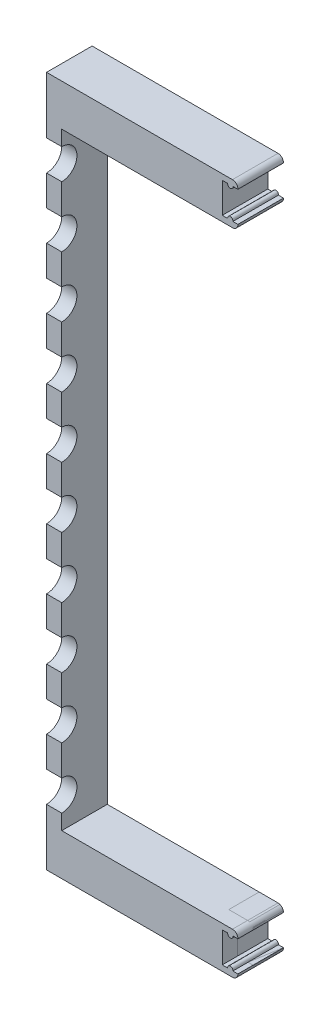
SolidWorks part; units mm, degrees
ref_plane "Front Plane" through (0, 0, 0) normal (0, 0, 1) x (1, 0, 0)
ref_plane "Top Plane" through (0, 0, 0) normal (0, 1, 0) x (1, 0, 0)
ref_plane "Right Plane" through (0, 0, 0) normal (1, 0, 0) x (0, 0, -1)
sketch "Sketch4" plane through (0, 0, 0) normal (0, 0, 1) x (1, 0, 0)
  line L0 (0, 0) -> (0, 13.7)
  line L1 (0, 13.7) -> (6.2, 13.7)
  line L2 (8, 11.9) -> (8, 11.85)
  line L4 (8, 11.85) -> (2.85, 11.85)
  line L5 (2.85, 11.85) -> (2.85, 1.85)
  line L6 (2.85, 1.85) -> (8, 1.85)
  line L10 (5.5, 11.85) -> (5.5, 13.7) construction
  line L14 (8, 1.85) -> (8, 1.8)
  line L15 (6.2, 0) -> (0, 0)
  line L16 (2.85, 6.85) -> (8, 6.85) construction
  line L17 (0, 0) -> (-55, 0)
  line L18 (-55, 0) -> (-55, 227.4)
  line L19 (-55, 113.7) -> (0, 113.7) construction
  line L20 (-55, 113.7) -> (-50, 113.7)
  line L21 (0, 113.7) -> (0, 0) construction
  line L22 (-50, 213.7) -> (-50, 13.7)
  line L23 (-50, 13.7) -> (0, 13.7)
  line L24 (2.85, 220.55) -> (8, 220.55) construction
  line L25 (5.5, 215.55) -> (5.5, 213.7) construction
  line L26 (-50, 213.7) -> (0, 213.7)
  line L27 (0, 227.4) -> (-55, 227.4)
  line L28 (6.2, 227.4) -> (0, 227.4)
  line L29 (8, 225.55) -> (8, 225.6)
  line L30 (-50, 227.4) -> (-50, 0) construction
  line L31 (2.85, 225.55) -> (8, 225.55)
  line L32 (2.85, 215.55) -> (2.85, 225.55)
  line L33 (8, 215.55) -> (2.85, 215.55)
  line L35 (8, 215.5) -> (8, 215.55)
  line L36 (0, 213.7) -> (6.2, 213.7)
  line L37 (0, 227.4) -> (0, 213.7)
  arc A2 (4.6633, 11.85) -> (6.3367, 11.85) centre (5.5, 11.7) ccw
  arc A3 (4.6633, 1.85) -> (6.3367, 1.85) centre (5.5, 2) cw
  arc A4 (8, 11.9) -> (6.2, 13.7) centre (6.2, 11.9) ccw
  arc A5 (6.2, 0) -> (8, 1.8) centre (6.2, 1.8) ccw
  arc A12 (6.2, 227.4) -> (8, 225.6) centre (6.2, 225.6) cw
  arc A13 (8, 215.5) -> (6.2, 213.7) centre (6.2, 215.5) cw
  arc A14 (4.6633, 225.55) -> (6.3367, 225.55) centre (5.5, 225.4) ccw
  arc A15 (4.6633, 215.55) -> (6.3367, 215.55) centre (5.5, 215.7) cw
  point P7 (2.85, 6.85)
  point P15 (8, 13.7)
  point P26 (8, 13.7)
  point P29 (8, 0)
  point P37 (0, 13.7)
  point P40 (0, 0)
  point P73 (8, 227.4)
  point P74 (8, 213.7)
  dimension "D6" = 50
  dimension "D8" = 0.15
  dimension "D9" = 0.85
  dimension "D11" = 1.8
  dimension "D12" = 1.8
  dimension "D15" = 100
  dimension "D1" = 13.7
  dimension "D2" = 8
  dimension "D3" = 1.85
  dimension "D4" = 2.85
  dimension "D5" = 10
  dimension "D7" = 1.85
  dimension "D10" = 2.65
  dimension "D17" = 5
extrude "Boss-Extrude1" add sketch "Sketch4" along normal blind 10 contours L15 A5 L14 L6 L5 L4 L2 A4 L1 L0 | L4 A2 | A3 L6 region at (2.6177, 6.85, 0) region at (5.5, 2.2812, 0) region at (5.5, 11.4188, 0)
extrude "Boss-Extrude2" add sketch "Sketch4<5>" along normal blind 15 separate body contours L15 A5 L14 L6 L5 L4 L2 A4 L1 L0 | L23 L22 L20 L18 L17 L0 | L37 L27 L18 L20 L22 L26 | A13 L35 L33 L32 L31 L29 A12 L28 L37 L36 | L31 A14 | A15 L33 | A3 L6 | L4 A2 region at (-27.5, 1.263, 0) region at (2.6177, 6.85, 0) region at (-53.737, 170.55, 0) region at (5.5, 2.2812, 0) region at (2.6177, 220.55, 0) region at (5.5, 11.4188, 0) region at (5.5, 225.1188, 0) region at (5.5, 215.9812, 0)
sketch "Sketch4<5>" plane through (0, 0, 0) normal (0, 0, 1) x (1, 0, 0) same geometry as "Sketch4"
sketch "Sketch5" plane through (-55, 0, 0) normal (-1, 0, 0) x (0, 0, 1)
  line L0 (15, 113.7) -> (0, 113.7) construction
  line L1 (15, 0) -> (15, 227.4) construction
  line L2 (0, 0) -> (0, 227.4) construction
  line L3 (15, 113.7) -> (15, 108.7) construction
  line L4 (15, 88.7) -> (15, 78.7)
  line L5 (15, 108.7) -> (15, 98.7)
  line L6 (15, 68.7) -> (15, 58.7)
  line L7 (15, 48.7) -> (15, 38.7)
  line L8 (15, 28.7) -> (15, 18.7)
  line L9 (15, 98.7) -> (15, 78.7) construction
  line L10 (15, 118.7) -> (15, 128.7)
  line L11 (15, 198.7) -> (15, 208.7)
  line L12 (15, 178.7) -> (15, 188.7)
  line L13 (15, 158.7) -> (15, 168.7)
  line L14 (15, 138.7) -> (15, 148.7)
  arc A0 (15, 98.7) -> (15, 108.7) centre (15, 103.7) cw
  arc A1 (15, 78.7) -> (15, 88.7) centre (15, 83.7) cw
  arc A2 (15, 58.7) -> (15, 68.7) centre (15, 63.7) cw
  arc A3 (15, 38.7) -> (15, 48.7) centre (15, 43.7) cw
  arc A4 (15, 18.7) -> (15, 28.7) centre (15, 23.7) cw
  arc A5 (15, 128.7) -> (15, 118.7) centre (15, 123.7) ccw
  arc A6 (15, 208.7) -> (15, 198.7) centre (15, 203.7) ccw
  arc A7 (15, 188.7) -> (15, 178.7) centre (15, 183.7) ccw
  arc A8 (15, 168.7) -> (15, 158.7) centre (15, 163.7) ccw
  arc A9 (15, 148.7) -> (15, 138.7) centre (15, 143.7) ccw
  dimension "D1" = 5
  dimension "D4" = 5
  dimension "D3" = 20
  dimension "D2" = 10
extrude "Cut-Extrude4" cut sketch "Sketch5" against normal up to next (5 mm away)
